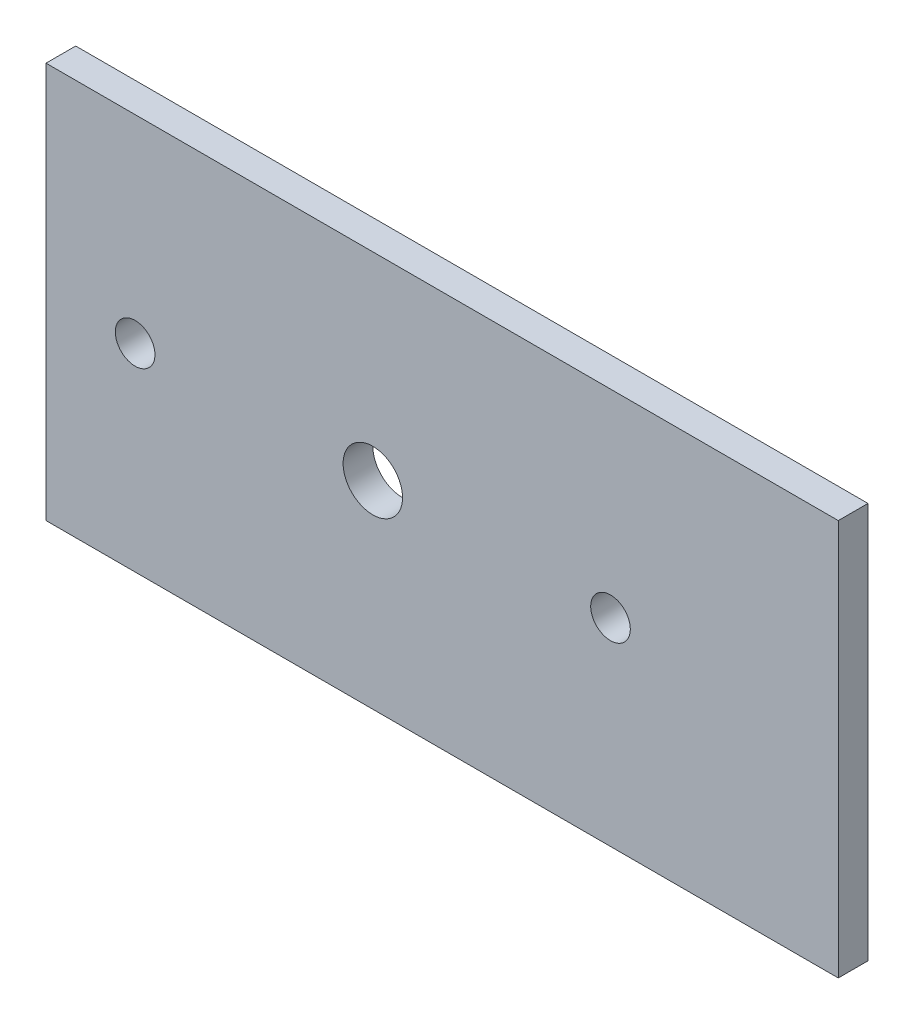
SolidWorks part; units mm, degrees
ref_plane "Front Plane" through (0, 0, 0) normal (0, 0, 1) x (1, 0, 0)
ref_plane "Top Plane" through (0, 0, 0) normal (0, 1, 0) x (1, 0, 0)
ref_plane "Right Plane" through (0, 0, 0) normal (1, 0, 0) x (0, 0, -1)
sketch "Sketch1" plane through (0, 0, 0) normal (0, 0, 1) x (1, 0, 0)
  line L1 (0, 0) -> (80, 0)
  line L2 (0, 0) -> (0, 40)
  line L3 (0, 40) -> (80, 40)
  line L4 (80, 0) -> (80, 40)
  dimension "D1" = 80
  dimension "D2" = 40
extrude "Boss-Extrude1" add sketch "Sketch1" along normal blind 3 contours L3 L4 L1 L2
sketch "Sketch2" plane through (0, 0, 3) normal (0, 0, 1) x (1, 0, 0)
  line L0 (0, 20) -> (80, 20) construction
  line L1 (0, 0) -> (0, 40) construction
  line L2 (80, 0) -> (80, 40) construction
  circle A0 centre (9, 20) radius 2
  circle A1 centre (33, 20) radius 3
  circle A2 centre (57, 20) radius 2
  dimension "D1" = 4
  dimension "D2" = 6
  dimension "D3" = 4
  dimension "D4" = 9
  dimension "D5" = 24
  dimension "D6" = 24
extrude "Cut-Extrude1" cut sketch "Sketch2" against normal through all contours A1 L0 | L0 A1 | A2 L0 | L0 A2 | A0 region at (57, 20.8488, 3) region at (57, 19.1512, 3) region at (33, 21.2732, 3) region at (33, 18.7268, 3)
ref_axis "Axis1" through (9, 20, 0) along (0, 0, 1)
